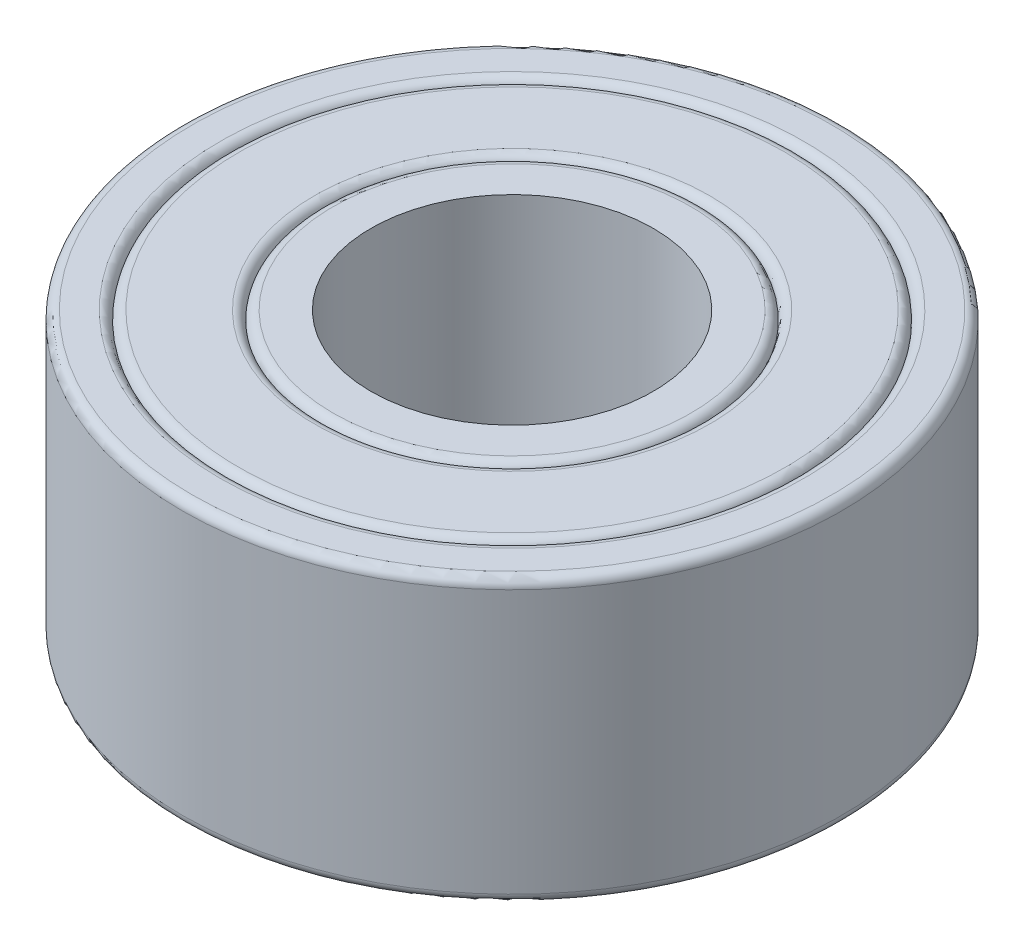
SolidWorks part; units mm, degrees
ref_plane "Front Plane" through (0, 0, 0) normal (0, 0, 1) x (1, 0, 0)
ref_plane "Top Plane" through (0, 0, 0) normal (0, 1, 0) x (1, 0, 0)
ref_plane "Right Plane" through (0, 0, 0) normal (1, 0, 0) x (0, 0, -1)
sketch "Sketch1" plane through (0, 0, 0) normal (0, 1, 0) x (1, 0, 0)
  circle A1 centre (0, 0) radius 1.5
  circle A2 centre (0, 0) radius 2
  dimension "D1" = 0.5
  dimension "D2" = 3
extrude "Boss-Extrude1" add sketch "Sketch1" along normal blind 3
fillet "Fillet1" radius 0.1 2 edges at (0, 3, 2) (0, 0, 2)
sketch "Sketch2" plane through (0, 0, 0) normal (0, -1, 0) x (1, 0, 0)
  circle A0 centre (0, 0) radius 2
  circle A1 centre (0, 0) radius 3
  dimension "D1" = 4
  dimension "D2" = 1
extrude "Boss-Extrude2" add sketch "Sketch2" against normal blind 3
fillet "Fillet2" radius 0.1 2 edges at (0, 0, -3) (0, 0, -2)
fillet "Fillet3" radius 0.1 2 edges at (0, 3, -2) (0, 3, -3)
sketch "Sketch3" plane through (0, 3, 0) normal (0, 1, 0) x (1, 0, 0)
  circle A0 centre (0, 0) radius 3.5
  circle A2 centre (0, 0) radius 3
  dimension "D1" = 7
extrude "Boss-Extrude3" add sketch "Sketch3" against normal blind 3
fillet "Fillet4" radius 0.1 4 edges at (0, 3, 3.5) (0, 0, 3.5) (0, 0, 3) (0, 3, 3)
